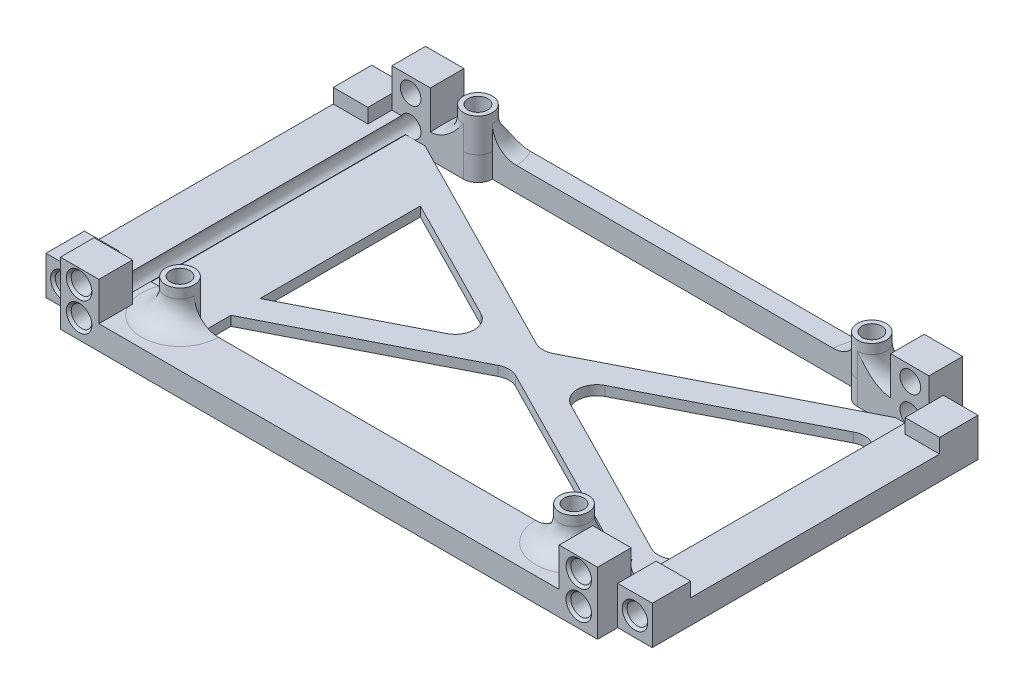
SolidWorks part; units mm, degrees
ref_plane "Front Plane" through (0, 0, 0) normal (0, 0, 1) x (1, 0, 0)
ref_plane "Top Plane" through (0, 0, 0) normal (0, 1, 0) x (1, 0, 0)
ref_plane "Right Plane" through (0, 0, 0) normal (1, 0, 0) x (0, 0, -1)
sketch "Sketch1" plane through (0, 0, 0) normal (0, 1, 0) x (1, 0, 0)
  line L0 (-70, -33.9) -> (-70, 33.9)
  line L1 (-70, -41) -> (70, -41) construction
  line L2 (-70, -41) -> (-70, 41) construction
  line L3 (-70, 41) -> (70, 41) construction
  line L4 (70, -41) -> (70, 41) construction
  line L5 (-70, -41) -> (70, 41) construction
  line L6 (-70, 41) -> (70, -41) construction
  line L7 (-70, 33.9) -> (-55.9, 33.9)
  line L8 (-55.9, 33.9) -> (-55.9, 41)
  line L9 (-55.9, 41) -> (55.9, 41)
  line L10 (55.9, 41) -> (55.9, 33.9)
  line L11 (55.9, 33.9) -> (70, 33.9)
  line L12 (70, 33.9) -> (70, -33.9)
  line L13 (70, -33.9) -> (55.9, -33.9)
  line L14 (55.9, -33.9) -> (55.9, -41)
  line L15 (55.9, -41) -> (-55.9, -41)
  line L16 (-55.9, -41) -> (-55.9, -33.9)
  line L17 (-55.9, -33.9) -> (-70, -33.9)
  point P0 (0, 0)
  dimension "D1" = 140
  dimension "D2" = 82
  dimension "D3" = 7.1
  dimension "D4" = 14.1
extrude "Boss-Extrude1" add sketch "Sketch1" along normal blind 5
sketch "Sketch3" plane through (0, 5, 0) normal (0, 1, 0) x (1, 0, 0)
  line L1 (-41, 33.9) -> (41, 33.9) construction
  line L2 (-41, 33.9) -> (-41, -28.1) construction
  line L3 (-41, -28.1) -> (41, -28.1) construction
  line L4 (41, 33.9) -> (41, -28.1) construction
  line L5 (-41, 33.9) -> (41, -28.1) construction
  line L6 (-41, -28.1) -> (41, 33.9) construction
  circle A0 centre (-41, -28.1) radius 3
  circle A1 centre (41, -28.1) radius 3
  circle A2 centre (41, 33.9) radius 3
  circle A3 centre (-41, 33.9) radius 3
  point P0 (0, 2.9)
  dimension "D4" = 6
  dimension "D1" = 82
  dimension "D2" = 62
  dimension "D3" = 2.9
sketch "Sketch2" plane through (0, 5, 0) normal (0, 1, 0) x (1, 0, 0)
  line L0 (-41, 30.9) -> (-38, 30.9)
  line L5 (-38, -28.1) -> (38, -28.1)
  line L6 (-41, -25.1) -> (-41, 30.9)
  line L7 (-38, 33.9) -> (38, 33.9)
  line L8 (41, -25.1) -> (41, 30.9)
  line L9 (-41, -28.1) -> (41, 33.9) construction
  line L10 (-41, 33.9) -> (41, -28.1) construction
  line L11 (-38, 30.9) -> (-38, 33.9)
  line L12 (38, 33.9) -> (38, 30.9)
  line L13 (38, 30.9) -> (41, 30.9)
  line L14 (41, -25.1) -> (38, -25.1)
  line L15 (38, -25.1) -> (38, -28.1)
  line L16 (-38, -28.1) -> (-38, -25.1)
  line L17 (-38, -25.1) -> (-41, -25.1)
  line L18 (41, -28.1) -> (-41, -28.1) construction
  line L19 (-41, -28.1) -> (-41, 33.9) construction
  line L20 (-41, 33.9) -> (41, 33.9) construction
  line L21 (41, 33.9) -> (41, -28.1) construction
  point P0 (0, 0)
  point P1 (0, 2.9)
  dimension "D1" = 3
extrude "Cut-Extrude1" cut sketch "Sketch2" against normal through all
extrude "Boss-Extrude2" add sketch "Sketch3" along normal blind 7
sketch "Sketch4" plane through (0, 12, 0) normal (0, 1, 0) x (1, 0, 0)
  circle A0 centre (-41, 33.9) radius 2.05
  circle A1 centre (41, 33.9) radius 2.05
  circle A2 centre (41, -28.1) radius 2.05
  circle A3 centre (-41, -28.1) radius 2.05
  dimension "D1" = 4.1
extrude "Cut-Extrude2" cut sketch "Sketch4" against normal through all and the other way through all
sketch "Sketch5" plane through (0, 5, 0) normal (0, 1, 0) x (1, 0, 0)
  line L0 (-41, -25.1) -> (-38, -25.1) construction
  line L1 (-41, 30.9) -> (-53, 30.9)
  line L2 (-41, 30.9) -> (-41, -25.1)
  line L3 (-41, -25.1) -> (-53, -25.1)
  line L4 (-53, 30.9) -> (-53, -25.1)
  line L5 (0, 33.9) -> (0, -28.1) construction
  line L6 (38, 33.9) -> (-38, 33.9) construction
  line L7 (-38, -28.1) -> (38, -28.1) construction
  line L8 (53, 30.9) -> (53, -25.1)
  line L9 (41, -25.1) -> (53, -25.1)
  line L10 (41, 30.9) -> (41, -25.1)
  line L11 (41, 30.9) -> (53, 30.9)
  dimension "D1" = 12
extrude "Cut-Extrude3" cut sketch "Sketch5" against normal through all
fillet "Fillet1" radius 3 4 edges at (38, 2.5, 25.1) (-38, 2.5, 25.1) (38, 2.5, -30.9) (-38, 2.5, -30.9)
sketch "Sketch6" plane through (0, 5, 0) normal (0, 1, 0) x (1, 0, 0)
  line L0 (38, 33.9) -> (-38, 33.9) construction
  line L1 (-25, 33.9) -> (25, 33.9)
  line L2 (-25, 33.9) -> (-25, 28.1)
  line L3 (-25, 28.1) -> (25, 28.1)
  line L4 (25, 33.9) -> (25, 28.1)
  line L5 (0, -28.1) -> (0, -41) construction
  line L6 (-38, -28.1) -> (38, -28.1) construction
  line L7 (-55.9, -41) -> (55.9, -41) construction
  line L8 (0, 28.1) -> (0, 41) construction
  line L9 (55.9, 41) -> (-55.9, 41) construction
  point P6 (0, 28.1)
  dimension "D1" = 50
sketch "Sketch7" plane through (0, 5, 0) normal (0, 1, 0) x (1, 0, 0)
  line L0 (0, 41) -> (0, -41) construction
  line L1 (55.9, 33.9) -> (63.1, 33.9)
  line L2 (55.9, 33.9) -> (55.9, 25.9)
  line L3 (55.9, 25.9) -> (63.1, 25.9)
  line L4 (63.1, 33.9) -> (63.1, 25.9)
  line L5 (55.9, 41) -> (-55.9, 41) construction
  line L6 (-55.9, -41) -> (55.9, -41) construction
  line L7 (-70, 0) -> (70, 0) construction
  line L8 (-70, 33.9) -> (-70, -33.9) construction
  line L9 (70, -33.9) -> (70, 33.9) construction
  dimension "D1" = 7.2
  dimension "D2" = 8
extrude "Boss-Extrude3" add sketch "Sketch7" along normal blind 3
sketch "Sketch8" plane through (0, 0, -33.9) normal (0, 0, -1) x (-1, 0, 0)
  line L0 (-63.1, 8) -> (-55.9, 0) construction
  circle A0 centre (-59.5, 4) radius 2.15
  dimension "D1" = 4.3
extrude "Cut-Extrude5" cut sketch "Sketch8" against normal blind 6
mirror "Mirror3" about plane through (0, 0, 0) normal (1, 0, 0) of "Cut-Extrude5", "Boss-Extrude3"
mirror "Mirror4" about plane through (0, 0, 0) normal (0, 0, 1) of "Mirror3", "Boss-Extrude3", "Cut-Extrude5"
sketch "Sketch10" plane through (0, 5, 0) normal (0, 1, 0) x (1, 0, 0)
  line L0 (55.9, 33.9) -> (55.9, 41) construction
  line L1 (-55.9, 41) -> (55.9, 41)
  line L2 (-55.9, 41) -> (-55.9, 40)
  line L3 (-55.9, 40) -> (55.9, 40)
  line L4 (55.9, 41) -> (55.9, 40)
  line L5 (-55.9, -33.9) -> (-55.9, -41) construction
  line L6 (55.9, -41) -> (-55.9, -41)
  line L7 (55.9, -41) -> (55.9, -40)
  line L8 (55.9, -40) -> (-55.9, -40)
  line L9 (-55.9, -41) -> (-55.9, -40)
  dimension "D1" = 1
  dimension "D2" = 1
extrude "Cut-Extrude7" cut sketch "Sketch10" against normal through all
sketch "Sketch13" plane through (0, 5, 0) normal (0, 1, 0) x (1, 0, 0)
  line L0 (55.9, 33.9) -> (55.9, 40) construction
  line L1 (-55.9, 40) -> (55.9, 40)
  line L2 (-55.9, 40) -> (-55.9, 39.4)
  line L3 (-55.9, 39.4) -> (55.9, 39.4)
  line L4 (55.9, 40) -> (55.9, 39.4)
  line L5 (-55.9, -33.9) -> (-55.9, -40) construction
  line L6 (55.9, -40) -> (-55.9, -40)
  line L7 (55.9, -40) -> (55.9, -39.6)
  line L8 (55.9, -39.6) -> (-55.9, -39.6)
  line L9 (-55.9, -40) -> (-55.9, -39.6)
  dimension "D1" = 0.6
  dimension "D2" = 0.4
extrude "Cut-Extrude9" cut sketch "Sketch13" against normal through all both and the other way through all
sketch "Sketch14" plane through (0, 5, 0) normal (0, 1, 0) x (1, 0, 0)
  line L0 (-41, 30.9) -> (-53, 30.9) construction
  line L1 (-55.9, -39.6) -> (-47.9, -39.6)
  line L2 (-55.9, -39.6) -> (-55.9, -31.1)
  line L3 (-55.9, -31.1) -> (-47.9, -31.1)
  line L4 (-47.9, -39.6) -> (-47.9, -31.1)
  line L5 (-55.9, 39.4) -> (-47.9, 39.4)
  line L6 (-55.9, 39.4) -> (-55.9, 30.9)
  line L7 (-55.9, 30.9) -> (-47.9, 30.9)
  line L8 (-47.9, 39.4) -> (-47.9, 30.9)
  dimension "D1" = 8
extrude "Boss-Extrude5" add sketch "Sketch14" along normal blind 8
sketch "Sketch15" plane through (0, 0, 39.6) normal (0, 0, 1) x (1, 0, 0)
  line L0 (-47.9, 5) -> (-47.9, 0) construction
  line L1 (55.9, 0) -> (-55.9, 0) construction
  line L3 (-55.9, 0) -> (-55.9, 13) construction
  circle A0 centre (-52, 4) radius 2.15
  circle A1 centre (-52, 10) radius 2.15
  dimension "D1" = 4.3
  dimension "D2" = 3.9
  dimension "D3" = 6
  dimension "D4" = 4
extrude "Cut-Extrude10" cut sketch "Sketch15" against normal through all
mirror "Mirror5" about plane through (0, 0, 0) normal (1, 0, 0) of "Boss-Extrude5", "Cut-Extrude10"
sketch "Sketch16" plane through (0, 13, 0) normal (0, 1, 0) x (1, 0, 0)
  line L0 (55.9, -79.1) -> (55.9, 39.4) construction
  line L1 (-55.9, 39.4) -> (55.9, 39.4)
  line L2 (-55.9, 39.4) -> (-55.9, 37.9)
  line L3 (-55.9, 37.9) -> (55.9, 37.9)
  line L4 (55.9, 39.4) -> (55.9, 37.9)
  line L5 (-55.9, -31.1) -> (-55.9, -39.6) construction
  line L6 (55.9, -39.6) -> (-55.9, -39.6)
  line L7 (55.9, -39.6) -> (55.9, -38.1)
  line L8 (55.9, -38.1) -> (-55.9, -38.1)
  line L9 (-55.9, -39.6) -> (-55.9, -38.1)
  dimension "D1" = 1.5
  dimension "D2" = 1.5
extrude "Cut-Extrude11" cut sketch "Sketch16" against normal through all
fillet "Fillet2" radius 5 4 edges at (43.1213, 5, -36.0213) (-43.1213, 5, -36.0213) (43.1213, 5, 30.2213) (-43.1213, 5, 30.2213)
sketch "Sketch17" plane through (0, 0, 0) normal (0, -1, 0) x (1, 0, 0)
  line L0 (-53, 21.1) -> (-5.9231, -2.9)
  line L1 (-53, -30.9) -> (-53, 25.1) construction
  line L2 (53, -30.9) -> (41, -30.9) construction
  line L3 (49, -30.9) -> (53, -30.9)
  line L4 (53, -30.9) -> (53, -26.9)
  line L5 (53, 25.1) -> (53, -30.9) construction
  line L6 (53, -26.9) -> (5.9231, -2.9)
  line L7 (-53, 25.1) -> (-41, 25.1) construction
  line L8 (-49, 25.1) -> (-53, 25.1)
  line L9 (-53, 25.1) -> (-53, 21.1)
  line L10 (-53, -30.9) -> (-49, -30.9)
  line L11 (-41, -30.9) -> (-53, -30.9) construction
  line L12 (-49, -30.9) -> (0, -5.9196)
  line L13 (53, 21.1) -> (53, 25.1)
  line L14 (53, 25.1) -> (49, 25.1)
  line L15 (41, 25.1) -> (53, 25.1) construction
  line L16 (49, 25.1) -> (0, 0.1196)
  line L17 (-53, -26.9) -> (-53, -30.9)
  line L18 (-5.9231, -2.9) -> (-53, -26.9)
  line L19 (5.9231, -2.9) -> (53, 21.1)
  line L20 (0, 0.1196) -> (-49, 25.1)
  line L21 (0, -5.9196) -> (49, -30.9)
  dimension "D1" = 4
extrude "Boss-Extrude6" add sketch "Sketch17" against normal blind 2
fillet "Fillet3" radius 4 8 edges at (5.9231, 1, -2.9) (0, 1, 0.1196) (0, 1, -5.9196) (53, 1, -26.9) (53, 1, 21.1) (-53, 1, 21.1) (-5.9231, 1, -2.9) (-53, 1, -26.9)
chamfer "Chamfer1" distance 0.5 angle 45 12 edges at (49.85, 4, 38.1) (49.85, 10, 38.1) (57.35, 4, 33.9) (-54.15, 10, 38.1) (-54.15, 4, 38.1) (-57.35, 4, 33.9) (57.35, 4, -33.9) (-57.35, 4, -33.9) (-49.85, 10, -37.9) (-49.85, 4, -37.9) (54.15, 4, -37.9) (54.15, 10, -37.9)
sketch "Sketch18" plane through (0, 2, 0) normal (0, 1, 0) x (1, 0, 0)
  line L0 (-53, 20.371) -> (-53, 30.9) construction
  line L1 (-53, 25.6355) -> (-38.6735, 25.6355)
  line L2 (-53, 25.6355) -> (-53, -25.6355)
  line L3 (-53, -25.6355) -> (-38.6735, -25.6355)
  line L4 (-38.6735, 25.6355) -> (-38.6735, -25.6355)
  line L5 (-49, 30.9) -> (-1.8167, 6.8458) construction
  point P6 (-38.6735, 0)
extrude "Boss-Extrude7" add sketch "Sketch18" against normal up to surface (2 mm away) up to face at (37.6676, 0, -2.9)
sketch "Sketch19" plane through (0, 5, 0) normal (0, 1, 0) x (1, 0, 0)
  line L1 (-70, 33.9) -> (-63.1, 33.9)
  line L2 (-70, 33.9) -> (-70, -33.9)
  line L3 (-70, -33.9) -> (-63.1, -33.9)
  line L4 (-63.1, 33.9) -> (-63.1, -33.9)
  line L5 (70, 33.9) -> (63.1, 33.9)
  line L6 (70, 33.9) -> (70, -33.9)
  line L7 (70, -33.9) -> (63.1, -33.9)
  line L8 (63.1, 33.9) -> (63.1, -33.9)
extrude "Cut-Extrude12" cut sketch "Sketch19" against normal through all
